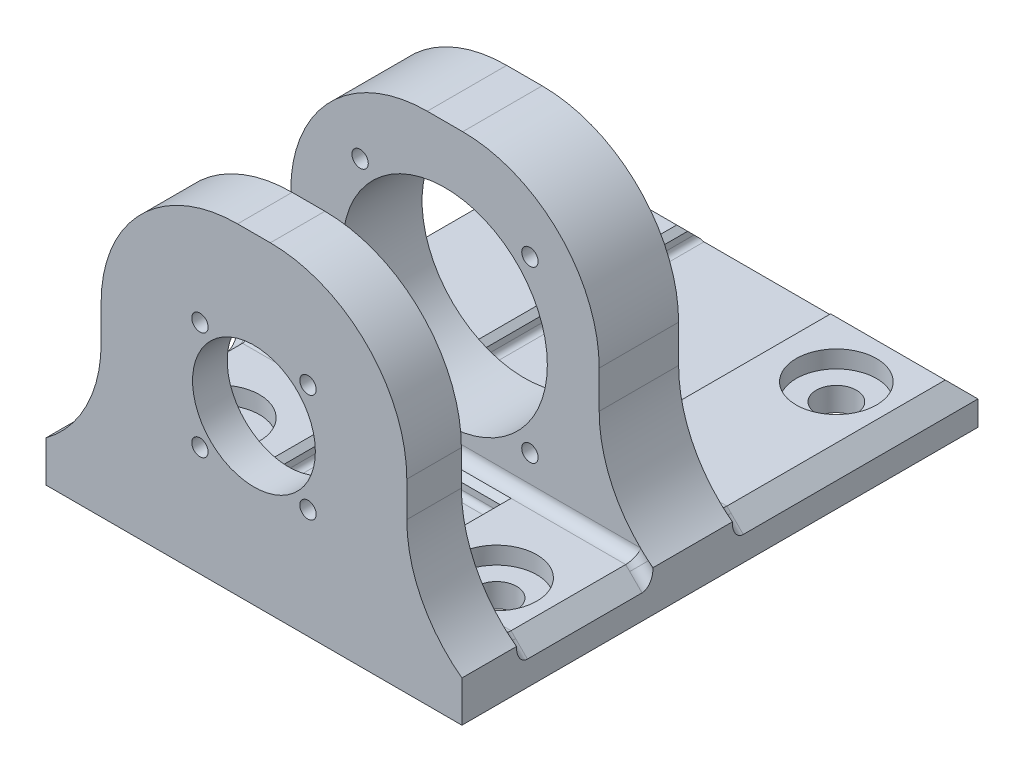
SolidWorks part; units mm, degrees
ref_plane "Front Plane" through (0, 0, 0) normal (0, 0, 1) x (1, 0, 0)
ref_plane "Top Plane" through (0, 0, 0) normal (0, 1, 0) x (1, 0, 0)
ref_plane "Right Plane" through (0, 0, 0) normal (1, 0, 0) x (0, 0, -1)
sketch "Sketch1" plane through (0, 0, 0) normal (0, 0, 1) x (1, 0, 0)
  line L0 (0, 0) -> (9.8995, 9.8995) construction
  line L1 (-21, -30) -> (21, -30)
  line L2 (-21, -30) -> (-21, 22)
  line L3 (-21, 22) -> (21, 22)
  line L4 (21, -30) -> (21, 22)
  line L5 (0, 0) -> (9.8995, -9.8995) construction
  line L6 (0, 0) -> (-9.8995, 9.8995) construction
  line L7 (0, 0) -> (-9.8995, -9.8995) construction
  circle A0 centre (0, 0) radius 11.25
  circle A1 centre (0, 0) radius 14 construction
  circle A2 centre (-9.8995, 9.8995) radius 1.5
  circle A3 centre (9.8995, 9.8995) radius 1.5
  circle A4 centre (-9.8995, -9.8995) radius 1.5
  circle A5 centre (9.8995, -9.8995) radius 1.5
  dimension "D1" = 22.5
  dimension "D2" = 42
  dimension "D3" = 28
  dimension "D4" = 3
  dimension "D5" = 22
  dimension "D6" = 52
  dimension "D7" = 21
extrude "Boss-Extrude1" add sketch "Sketch1" along normal blind 6.35
sketch "Sketch2" plane through (0, 0, 0) normal (0, 0, -1) x (-1, 0, 0)
  line L1 (-21, -30) -> (21, -30)
  line L2 (-21, -30) -> (-21, 22)
  line L3 (-21, 22) -> (21, 22)
  line L4 (21, -30) -> (21, 22)
  circle A0 centre (0, 0) radius 18.75
  dimension "D1" = 37.5
extrude "Boss-Extrude2" add sketch "Sketch2" along normal blind 43.2
sketch "Sketch3" plane through (0, 22, 0) normal (0, 1, 0) x (1, 0, 0)
  line L0 (-21, -6.35) -> (-21, 43.2) construction
  line L1 (-21, 3.65) -> (21, 3.65)
  line L2 (-21, 3.65) -> (-21, 28.65)
  line L3 (-21, 28.65) -> (21, 28.65)
  line L4 (21, 3.65) -> (21, 28.65)
  line L5 (21, -6.35) -> (21, 43.2) construction
  line L6 (21, -6.35) -> (-21, -6.35) construction
  dimension "D1" = 10
  dimension "D2" = 25
extrude "Cut-Extrude1" cut sketch "Sketch3" against normal offset from surface (44.5 mm away) 7.5 up to face at (0, -30, -18.425)
sketch "Sketch4" plane through (0, 0, -43.2) normal (0, 0, -1) x (-1, 0, 0)
  line L0 (0, 0) -> (-15.5563, 15.5563) construction
  line L1 (0, 0) -> (15.5563, 15.5563) construction
  line L2 (0, 0) -> (15.5563, -15.5563) construction
  line L3 (0, 0) -> (-15.5563, -15.5563) construction
  line L5 (-21.15, -21.15) -> (21.15, -21.15) construction
  line L6 (-21.15, -21.15) -> (-21.15, 21.15) construction
  line L7 (-21.15, 21.15) -> (21.15, 21.15) construction
  line L8 (21.15, -21.15) -> (21.15, 21.15) construction
  line L9 (-21.15, -21.15) -> (21.15, 21.15) construction
  line L10 (-21.15, 21.15) -> (21.15, -21.15) construction
  circle A0 centre (0, 0) radius 22 construction
  circle A1 centre (-15.5563, 15.5563) radius 1.5
  circle A2 centre (15.5563, 15.5563) radius 1.5
  circle A3 centre (15.5563, -15.5563) radius 1.5
  circle A4 centre (-15.5563, -15.5563) radius 1.5
  point P14 (0, 0)
  dimension "D1" = 3
  dimension "D3" = 42.3
  dimension "D4" = 42.3
  dimension "D2" = 4
extrude "Cut-Extrude2" cut sketch "Sketch4" against normal up to surface (14.55 mm away) up to face at (-18.75, 0, -28.65)
sketch "Sketch5" plane through (0, -30, 0) normal (0, -1, 0) x (1, 0, 0)
  line L0 (0, -43.2) -> (0, 6.35) construction
  line L1 (0, -74.95) -> (25.4, -74.95) construction
  line L2 (21, -43.2) -> (-21, -43.2) construction
  line L3 (-21, 6.35) -> (21, 6.35) construction
  line L4 (0, -12.7) -> (-25.4, -12.7) construction
  line L5 (0, -12.7) -> (25.4, -12.7) construction
  line L6 (0, 6.35) -> (-38.1, 6.35) construction
  line L7 (0, 6.35) -> (38.1, 6.35) construction
  line L10 (21, 6.35) -> (21, -43.2) construction
  line L11 (38.1, 6.35) -> (21, 6.35)
  line L12 (38.1, 6.35) -> (38.1, -88.2)
  line L13 (38.1, -88.2) -> (21, -88.2)
  line L14 (21, 6.35) -> (21, -88.2)
  line L15 (-21, 6.35) -> (-21, -43.2) construction
  line L16 (-38.1, 6.35) -> (-21, 6.35)
  line L17 (-38.1, 6.35) -> (-38.1, -55.9)
  line L19 (-21, 6.35) -> (-21, -55.9)
  line L21 (0, -74.95) -> (-25.4, -74.95) construction
  line L22 (21, -43.2) -> (-21, -43.2)
  line L23 (21, -43.2) -> (21, -88.2)
  line L24 (21, -88.2) -> (-21, -88.2)
  line L25 (-21, -43.2) -> (-21, -88.2)
  line L26 (-38.1, -55.9) -> (-38.1, -88.2)
  line L27 (-38.1, -88.2) -> (-21, -88.2)
  circle A0 centre (-25.4, -12.7) radius 3.683
  circle A1 centre (25.4, -12.7) radius 3.683
  circle A4 centre (25.4, -74.95) radius 3.683
  circle A5 centre (-25.4, -74.95) radius 3.683
  line M7 (-21, 6.35) -> (-21, -43.2)
  line M8 (-21, -43.2) -> (21, -43.2)
  line M9 (21, -43.2) -> (21, 6.35)
  dimension "D7" = 7.366
  dimension "D8" = 7.366
  dimension "D13" = 7.366
  dimension "D14" = 7.366
  dimension "D19" = 31.75
  dimension "D1" = 25.4
  dimension "D2" = 25.4
  dimension "D3" = 38.1
  dimension "D4" = 38.1
  dimension "D5" = 45
  dimension "D9" = 19.05
  dimension "D17" = 25.4
  dimension "D18" = 25.4
extrude "Boss-Extrude3" add sketch "Sketch5" against normal up to surface (7.5 mm away) contours L19 L25 L24 L23 L14 M8 | L14 L13 L12 L11 A1 M9 | L19 L16 L17 A0 M7 region at (29.7809, -30, -40.7636) region at (0, -30, -65.7) region at (-29.7809, -30, -40.7636) up to face at (0, -22.5, -16.15)
sketch "Sketch6" plane through (0, 0, -43.2) normal (0, 0, -1) x (-1, 0, 0)
  line L1 (-21.25, 22.25) -> (-21.25, -22.75)
  line L2 (-21.25, -22.75) -> (21.25, -22.75)
  line L3 (21.25, -22.75) -> (21.25, 22.25)
  line L4 (21.25, 22.25) -> (-21.25, 22.25)
  line L5 (-21, 22) -> (-21, -22.5)
  line L6 (-21, -22.5) -> (21, -22.5)
  line L7 (21, -22.5) -> (21, 22)
  line L8 (21, 22) -> (-21, 22)
  line L10 (-21, 22) -> (-21, -22.5)
  line L11 (-21, -22.5) -> (21, -22.5)
  line L12 (21, -22.5) -> (21, 22)
  line L13 (21, 22) -> (-21, 22)
  dimension "D1" = 0
  dimension "D2" = 0.25
extrude "Boss-Extrude4" add sketch "Sketch6" against normal up to surface (14.55 mm away) up to face at (-17.0563, 15.5563, -28.65)
sketch "Sketch18" plane through (0, -22.5, 0) normal (0, 1, 0) x (1, 0, 0)
  line L0 (38.1, 88.2) -> (-38.1, 88.2) construction
  line L1 (13.1, 6.65) -> (-13.1, 6.65)
  line L2 (13.1, 6.65) -> (13.1, 25.65)
  line L3 (13.1, 25.65) -> (-13.1, 25.65)
  line L4 (-13.1, 6.65) -> (-13.1, 25.65)
  line L5 (13.1, 46.2) -> (-13.1, 46.2)
  line L6 (13.1, 46.2) -> (13.1, 88.2)
  line L7 (13.1, 88.2) -> (-13.1, 88.2)
  line L8 (-13.1, 46.2) -> (-13.1, 88.2)
  line L9 (-38.1, -6.35) -> (-38.1, 88.2) construction
  line L10 (38.1, -6.35) -> (38.1, 88.2) construction
  line L11 (21, 3.65) -> (-21, 3.65) construction
  line L12 (-21.25, 28.65) -> (21.25, 28.65) construction
  line L13 (-21.25, 43.2) -> (21.25, 43.2) construction
  circle A0 centre (25.4, 74.95) radius 7.366
  circle A1 centre (-25.4, 74.95) radius 7.366
  circle A2 centre (25.4, 12.7) radius 7.366
  circle A3 centre (-25.4, 12.7) radius 7.366
  dimension "D1" = 14.732
  dimension "D2" = 14.732
  dimension "D3" = 14.732
  dimension "D4" = 14.732
  dimension "D5" = 25
  dimension "D6" = 25
  dimension "D7" = 25
  dimension "D8" = 25
  dimension "D9" = 3
  dimension "D10" = 3
  dimension "D11" = 3
extrude "Cut-Extrude3" cut sketch "Sketch18" against normal blind 3.175
sketch "Sketch19" plane through (0, 0, -43.2) normal (0, 0, -1) x (-1, 0, 0)
  line L0 (-28.25, 29.25) -> (-28.25, -29.5)
  line L1 (-28.25, -29.5) -> (28.25, -29.5)
  line L2 (28.25, -29.5) -> (28.25, 29.25)
  line L3 (28.25, 29.25) -> (-28.25, 29.25)
  line L4 (-21.25, 22.25) -> (-21.25, -22.5)
  line L5 (-21.25, -22.5) -> (21.25, -22.5)
  line L6 (21.25, -22.5) -> (21.25, 22.25)
  line L7 (21.25, 22.25) -> (-21.25, 22.25)
  line L8 (-21.25, 22.25) -> (-21.25, -22.5)
  line L9 (-21.25, -22.5) -> (21.25, -22.5)
  line L10 (21.25, -22.5) -> (21.25, 22.25)
  line L11 (21.25, 22.25) -> (-21.25, 22.25)
  line M10 (-21.25, -22.5) -> (21.25, -22.5)
  line M22 (-21.25, 22.25) -> (-21.25, -22.5)
  line M23 (21.25, -22.5) -> (21.25, 22.25)
  line M24 (21.25, 22.25) -> (-21.25, 22.25)
  dimension "D1" = 0
  dimension "D2" = 7
extrude "Boss-Extrude5" add sketch "Sketch19" against normal up to surface (14.55 mm away) contours L2 L3 L0 L1 M22 M24 M23 M10 region at (0, 28.4349, -43.2) up to face at (-17.0563, 15.5563, -28.65)
sketch "Sketch20" plane through (0, 0, -3.65) normal (0, 0, -1) x (-1, 0, 0)
  line L0 (-28, -29.5) -> (28, -29.5)
  line L1 (28, -29.5) -> (28, 29)
  line L2 (28, 29) -> (-28, 29)
  line L3 (-28, 29) -> (-28, -29.5)
  line L4 (-21, -22.5) -> (21, -22.5)
  line L5 (21, -22.5) -> (21, 22)
  line L6 (21, 22) -> (-21, 22)
  line L7 (-21, 22) -> (-21, -22.5)
  line L8 (-21, -22.5) -> (21, -22.5)
  line L9 (21, -22.5) -> (21, 22)
  line L10 (21, 22) -> (-21, 22)
  line L11 (-21, 22) -> (-21, -22.5)
  line M10 (21, 22) -> (-21, 22)
  line M11 (-21, 22) -> (-21, -22.5)
  line M13 (21, -22.5) -> (21, 22)
  dimension "D1" = 0
  dimension "D2" = 7
extrude "Boss-Extrude6" add sketch "Sketch20" against normal up to surface (10 mm away) contours L1 M11 M10 M13 region at (27.1902, -0.25, -3.65) up to face at (0, -13.25, 6.35)
fillet "Fillet9" radius 25 8 edges at (-28, -22.5, 1.35) (-28, 29, 1.35) (28, 29, 1.35) (28, -22.5, 1.35) (28.25, -22.5, -35.925) (-28.25, -22.5, -35.925) (-28.25, 29.25, -35.925) (28.25, 29.25, -35.925)
chamfer "Chamfer5" distance 3 angle 45 6 edges at (38.1, -22.5, -16.15) (38.1, -22.5, -65.7) (-38.1, -22.5, -16.15) (-38.1, -22.5, -65.7) (25.6, -22.5, -88.2) (-25.6, -22.5, -88.2)
fillet "Fillet10" radius 2 9 edges at (36.6, -24, -28.65) (36.6, -24, -3.65) (36.6, -24, -43.2) (-36.6, -24, -3.65) (-36.6, -24, -28.65) (-36.6, -24, -43.2) (0, -22.5, -28.65) (0, -22.5, -3.65) (0, -22.5, -43.2)
chamfer "Chamfer6" distance 1 angle 45 7 edges at (-13.1, -22.5, -65.7) (0, -22.5, -46.2) (13.1, -22.5, -65.7) (0, -22.5, -25.65) (13.1, -22.5, -16.15) (-13.1, -22.5, -16.15) (0, -22.5, -6.65)
fillet "Fillet11" radius 1 7 edges at (0, -25.675, -6.65) (-13.1, -25.675, -16.15) (0, -25.675, -25.65) (13.1, -25.675, -16.15) (13.1, -25.675, -67.2) (-13.1, -25.675, -67.2) (0, -25.675, -46.2)
